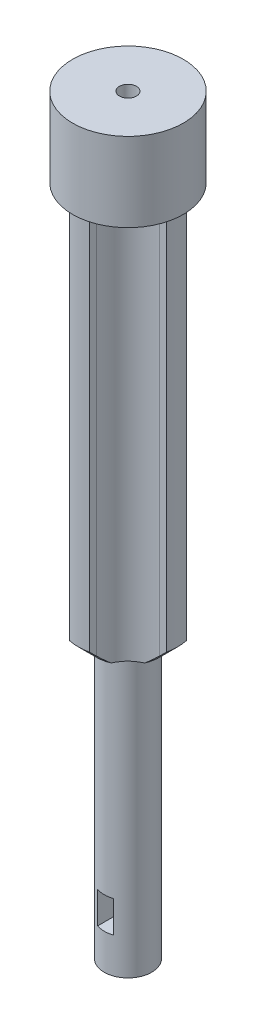
SolidWorks part; units mm, degrees
ref_plane "前视基准面" through (0, 0, 0) normal (0, 0, 1) x (1, 0, 0)
ref_plane "上视基准面" through (0, 0, 0) normal (0, 1, 0) x (1, 0, 0)
ref_plane "右视基准面" through (0, 0, 0) normal (1, 0, 0) x (0, 0, -1)
sketch "草图1" plane through (0, 0, 0) normal (0, 1, 0) x (1, 0, 0)
  circle A0 centre (0, 0) radius 14
  dimension "D1" = 28
extrude "凸台-拉伸1" add sketch "草图1" along normal blind 20
sketch "草图2" plane through (0, 0, 0) normal (0, -1, 0) x (1, 0, 0)
  line L1 (-12.2474, -2.5) -> (12.2474, -2.5)
  line L2 (-12.2474, -2.5) -> (-12.2474, 2.5)
  line L3 (-12.2474, 2.5) -> (12.2474, 2.5)
  line L4 (12.2474, -2.5) -> (12.2474, 2.5)
  line L5 (-12.2474, -2.5) -> (12.2474, 2.5) construction
  line L6 (-12.2474, 2.5) -> (12.2474, -2.5) construction
  line L7 (-2.5, -12.2474) -> (2.5, -12.2474)
  line L8 (-2.5, -12.2474) -> (-2.5, 12.2474)
  line L9 (-2.5, 12.2474) -> (2.5, 12.2474)
  line L10 (2.5, -12.2474) -> (2.5, 12.2474)
  line L11 (-2.5, -12.2474) -> (2.5, 12.2474) construction
  line L12 (-2.5, 12.2474) -> (2.5, -12.2474) construction
  circle A0 centre (0, 0) radius 12.5
  dimension "D2" = 25
  dimension "D1" = 5
extrude "凸台-拉伸2" add sketch "草图2" along normal blind 100 contours L3 L10 L9 L8 | L1 L8 L3 L2 | L1 L10 L3 L8 | L10 L1 L4 L3 | L7 L10 L1 L8 | L2 A0 | L9 A0 | L7 A0 | L4 A0 region at (-7.3737, 0, 0) region at (-12.3486, 0, 0) region at (0, 0, 0) region at (0, 0, -7.3737) region at (0, 0, -12.3486) region at (7.3737, 0, 0) region at (0, 0, 7.3737) region at (0, 0, 12.3486) region at (12.3486, 0, 0)
fillet "圆角1" radius 8 4 edges at (2.5, -50, -2.5) (-2.5, -50, -2.5) (-2.5, -50, 2.5) (2.5, -50, 2.5)
sketch "草图3" plane through (0, -100, 0) normal (0, -1, 0) x (1, 0, 0)
  circle A0 centre (0, 0) radius 6
  dimension "D1" = 12
extrude "凸台-拉伸3" add sketch "草图3" along normal blind 70
chamfer "倒角1" distance 4.5 angle 45 4 edges at (12.5, -100, 0) (0, -100, -12.5) (-12.5, -100, 0) (0, -100, 12.5)
chamfer "倒角2" [suppressed] distance 3 angle 45
sketch "草图4" plane through (0, 20, 0) normal (0, 1, 0) x (1, 0, 0)
  circle A0 centre (0, 0) radius 2.15
  dimension "D1" = 4.3
extrude "切除-拉伸1" cut sketch "草图4" against normal through all
sketch "草图5" plane through (0, 0, 0) normal (0, -1, 0) x (1, 0, 0)
  circle A0 centre (0, 0) radius 9
  dimension "D1" = 18
extrude "凸台-拉伸4" [suppressed] add sketch "草图5" along normal blind 4 from offset 40
sketch "草图6" plane through (0, 0, 0) normal (0, 0, 1) x (1, 0, 0)
  line L0 (-6, -170) -> (6, -170) construction
  line L1 (-6, -170) -> (6, -170) construction
  line L2 (0, -170) -> (0, -157) construction
  line L4 (-2, -161) -> (2, -161)
  line L5 (-2, -161) -> (-2, -153)
  line L6 (-2, -153) -> (2, -153)
  line L7 (2, -161) -> (2, -153)
  line L8 (-2, -161) -> (2, -153) construction
  line L9 (-2, -153) -> (2, -161) construction
  dimension "D1" = 4
  dimension "D2" = 8
  dimension "D3" = 9
extrude "切除-拉伸2" cut sketch "草图6" along normal through all
sketch "草图7" plane through (0, -161, 0) normal (0, 1, 0) x (1, 0, 0)
  circle A0 centre (0, 0) radius 6 construction
  circle A1 centre (0, 0) radius 6
extrude "凸台-拉伸5" add sketch "草图7" against normal blind 2
fillet "圆角4" radius 5 1 edges at (0, -153, 2.15)
